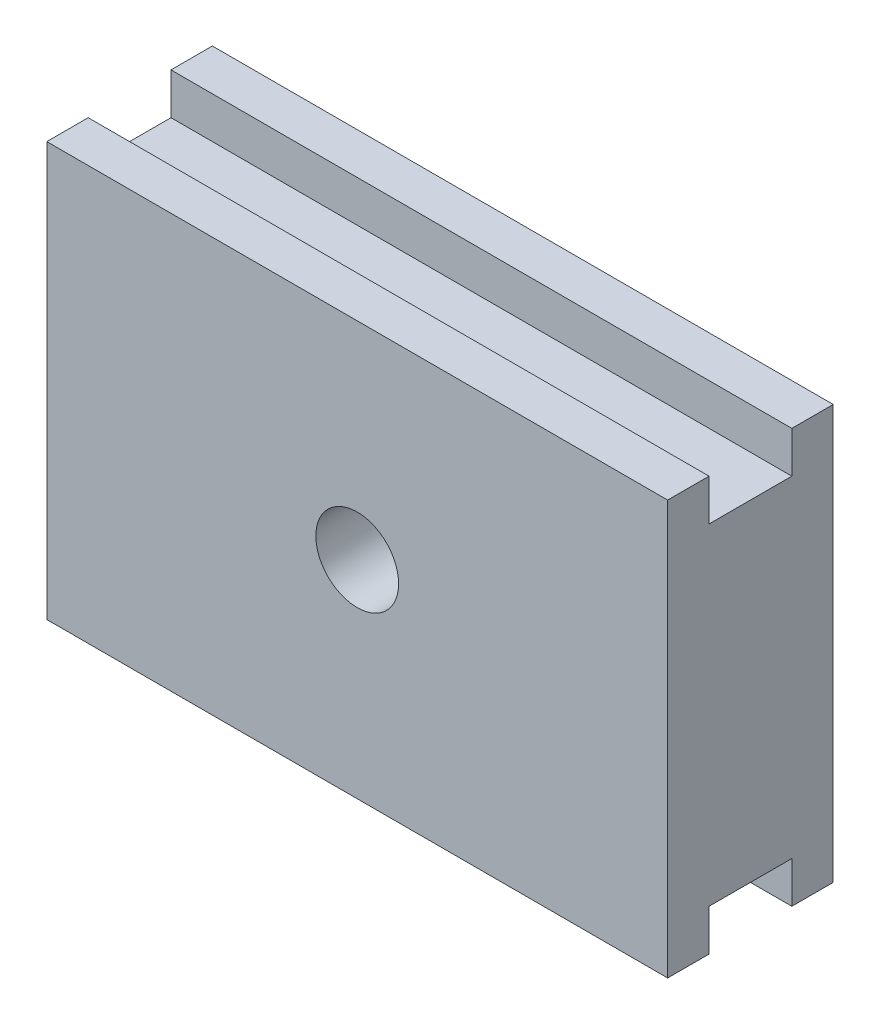
SolidWorks part; units mm, degrees
ref_plane "前视基准面" through (0, 0, 0) normal (0, 0, 1) x (1, 0, 0)
ref_plane "上视基准面" through (0, 0, 0) normal (0, 1, 0) x (1, 0, 0)
ref_plane "右视基准面" through (0, 0, 0) normal (1, 0, 0) x (0, 0, -1)
sketch "草图1" plane through (0, 0, 0) normal (0, 0, 1) x (1, 0, 0)
  line L1 (-7.5, 5) -> (7.5, 5)
  line L2 (-7.5, 5) -> (-7.5, -5)
  line L3 (-7.5, -5) -> (7.5, -5)
  line L4 (7.5, 5) -> (7.5, -5)
  line L5 (-7.5, 5) -> (7.5, -5) construction
  line L6 (-7.5, -5) -> (7.5, 5) construction
  point P0 (0, 0)
  dimension "D1" = 15
  dimension "D2" = 10
extrude "凸台-拉伸1" add sketch "草图1" along normal blind 4
sketch "草图2" plane through (7.5, 0, 0) normal (1, 0, 0) x (0, 0, -1)
  line L0 (-4, 5) -> (0, 5) construction
  line L1 (-1, 5) -> (-3, 5)
  line L2 (-1, 5) -> (-1, 4)
  line L3 (-1, -5) -> (-3, -5)
  line L4 (-3, 5) -> (-3, 4)
  line L5 (-4, -5) -> (0, -5) construction
  line L6 (-4, -5) -> (-4, 5) construction
  line L7 (0, -5) -> (0, 5) construction
  line L8 (-1, -4) -> (-3, -4)
  line L9 (-1, 4) -> (-3, 4)
  line L10 (-1, -4) -> (-1, -5)
  line L11 (-3, -4) -> (-3, -5)
  dimension "D1" = 1
  dimension "D2" = 1
  dimension "D3" = 1
  dimension "D4" = 1
extrude "切除-拉伸1" cut sketch "草图2" against normal through all
sketch "草图3" plane through (0, 0, 4) normal (0, 0, 1) x (1, 0, 0)
  circle A0 centre (0, 0) radius 1
extrude "切除-拉伸2" cut sketch "草图3" against normal through all
ref_plane "基准面1" through (0, 0.4706, 1.8824) normal (0, 0.2425, 0.9701) x (1, 0, 0)
ref_plane "基准面2" through (0, -0.4706, 1.8824) normal (0, -0.2425, 0.9701) x (1, 0, 0)
ref_axis "基准轴1" through (-8.25, 0, 2) along (1, 0, 0)
